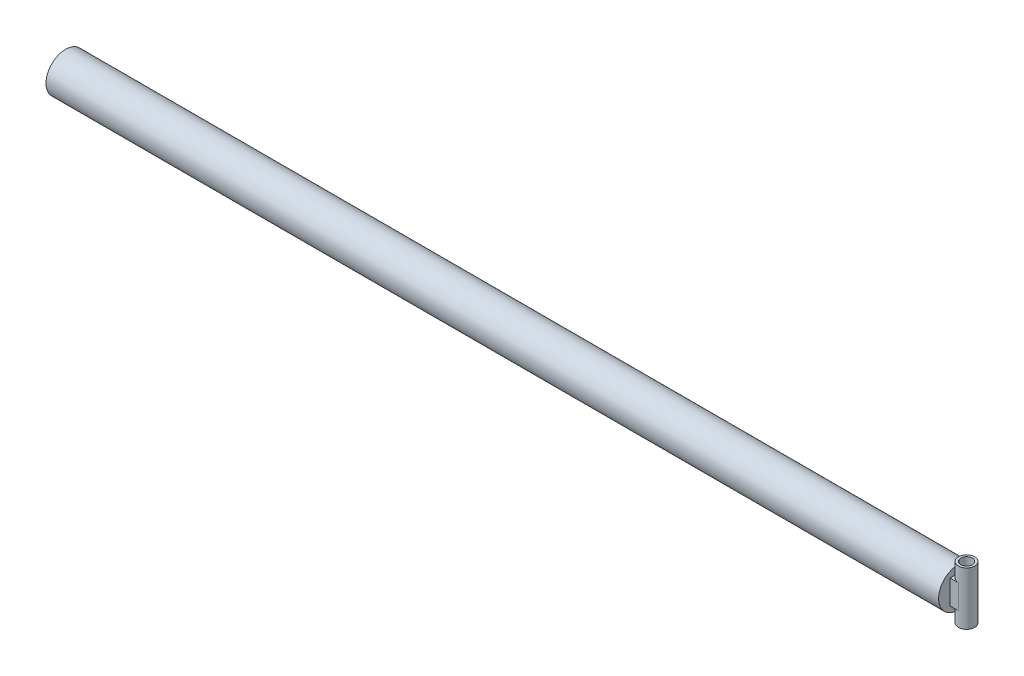
SolidWorks part; units mm, degrees
material "Plain Carbon Steel"
ref_plane "Front Plane" through (0, 0, 0) normal (0, 0, 1) x (1, 0, 0)
ref_plane "Top Plane" through (0, 0, 0) normal (0, 1, 0) x (1, 0, 0)
ref_plane "Right Plane" through (0, 0, 0) normal (1, 0, 0) x (0, 0, -1)
sketch "cilindar_Sketch2" plane through (0, 0, 0) normal (0, 1, 0) x (1, 0, 0)
  circle A0 centre (1966, 0) radius 35
  circle A1 centre (1966, 0) radius 25
  dimension "D2" = 70
  dimension "D3" = 50
  dimension "D1" = 1966
sketch "cilindar_Sketch1" plane through (0, 0, 0) normal (0, 1, 0) x (1, 0, 0)
  line L0 (-1930, 0) -> (1930, 0)
  line L1 (1930, 0) -> (1930, 75)
  line L2 (1930, 75) -> (1900, 75)
  line L3 (1900, 75) -> (1900, 85)
  line L4 (1900, 85) -> (-1900, 85)
  line L6 (-1900, 85) -> (-1900, 75)
  line L7 (-1900, 75) -> (-1930, 75)
  line L8 (-1930, 75) -> (-1930, 0)
  dimension "D1" = 85
  dimension "D3" = 30
  dimension "D2" = 3800
  dimension "D4" = 75
revolve "cilindar_Revolve1" add sketch "cilindar_Sketch1" angle 360 about L0 region at (0, 0, -42.4313)
shell "cilindar_Shell1" thickness 10 removed face at (-1930, 0, 75)
sketch "cilindar_Sketch3" plane through (0, 0, 0) normal (0, 1, 0) x (1, 0, 0)
  line L0 (-1900, 85) -> (-1900, -85) construction
  line L1 (-1900, 85) -> (-1900, -85) construction
  line L2 (-1930, 75) -> (-1930, -75) construction
  line L3 (-1930, 75) -> (-1930, -75) construction
  line L4 (-1930, 75) -> (-1900, 75)
  line L5 (-1900, 75) -> (-1900, 85)
  line L6 (-1900, 85) -> (-1930, 85)
  line L7 (-1930, 85) -> (-1930, 75)
ref_axis "cilindar_Axis1" through (1890, 0, 0) along (-1, 0, 0)
revolve "cilindar_Revolve2" add sketch "cilindar_Sketch3" angle 360 about axis through (1890, 0, 0) along (-1, 0, 0)
mirror "cilindar_Mirror2" about plane through (0, 0, 0) normal (1, 0, 0) of "cilindar_Revolve2"
extrude "cilindar_Boss-Extrude1" add sketch "cilindar_Sketch2" along normal blind 115 and the other way blind 115 separate body
sketch "cilindar_Sketch6" plane through (1930, 0, 0) normal (1, 0, 0) x (0, 0, -1)
  line L0 (-35, 115) -> (-35, -115) construction
  line L1 (35, -115) -> (35, 115) construction
  line L2 (-35, 115) -> (-35, -115) construction
  line L3 (35, -115) -> (35, 115) construction
  line L4 (35, 52.5) -> (35, -52.5)
  line L5 (-35, 52.5) -> (-35, -52.5) construction
  line L6 (35, 52.5) -> (-35, 52.5)
  line L7 (-35, -52.5) -> (35, 52.5) construction
  line L8 (35, -52.5) -> (-35, -52.5)
  line L9 (-35, 52.5) -> (-35, -52.5)
  dimension "D1" = 105
extrude "cilindar_Boss-Extrude7" add sketch "cilindar_Sketch6" along normal up to next
sketch "cilindar_Sketch7" plane through (-1930, 0, 0) normal (-1, 0, 0) x (0, 0, 1)
  circle A2 centre (0, 0) radius 18.75
  circle A3 centre (0, 0) radius 65 construction
  circle A4 centre (0, 0) radius 65
  dimension "D1" = 37.5
extrude "cilindar_Boss-Extrude8" add sketch "cilindar_Sketch7" against normal blind 10
equation "\"sirina_klipa\"= 150"
equation "\"debljina_klipa\"= 20"
equation "\"sirina_klipnjace\"= \"sirina_klipa\" / 4"
equation "\"duljina_klipnjace\"= 3800"
equation "\"r2_v\"= 70"
equation "\"r2_u\"= 50"
equation "\"r1_v\"= 70"
equation "\"r1_u\"= 50"
equation "\"l2\" = 190"
equation "\"l1\" = 230"
equation "\"sirina_cilindra\"= \"sirina_klipa\" + \"debljina_stijenke\" * 2"
equation "\"duljina_komore\"= 30"
equation "\"debljina_stijenke\"= 10"
equation "\"D3@cilindar_Sketch1\"= \"duljina_komore\""
equation "\"D4@cilindar_Sketch1\"=\"sirina_klipa\"/2"
equation "\"D1@cilindar_Sketch1\"=\"sirina_cilindra\"/2"
equation "\"D2@cilindar_Sketch1\"= \"duljina_cilindra\""
equation "\"D1@cilindar_Shell1\"=\"debljina_stijenke\""
equation "\"duljina_cilindra\"= \"duljina_klipnjace\" + \"debljina_klipa\" + \"debljina_stijenke\" - \"duljina_komore\""
equation "\"D1@cilindar_Sketch2\"=\"duljina_cilindra\"/2 + \"duljina_komore\" + \"r1_v\"/2 + 1"
equation "\"D2@cilindar_Sketch2\"=\"r1_v\""
equation "\"D3@cilindar_Sketch2\"=\"r1_u\""
equation "\"D1@cilindar_Sketch7\" = \"sirina_klipnjace\""
equation "\"D2@cilindar_Boss-Extrude1\"=\"l1\"/2"
equation "\"D1@cilindar_Boss-Extrude1\"=\"l1\"/2"
equation "\"D1@klip_Boss-Extrude1\"=\"debljina_klipa\""
equation "\"D1@klip_Sketch1\"=\"sirina_klipa\""
equation "\"D2@klip_Sketch3\"= \"duljina_klipnjace\" + \"r2_v\" / 2"
equation "\"D3@klip_Sketch3\" = \"r2_u\""
equation "\"D1@klip_Sketch3\"=\"r2_v\""
equation "\"D1@klip_Boss-Extrude3\" = \"l2\" / 2"
equation "\"D2@klip_Boss-Extrude3\" = \"l2\" / 2"
